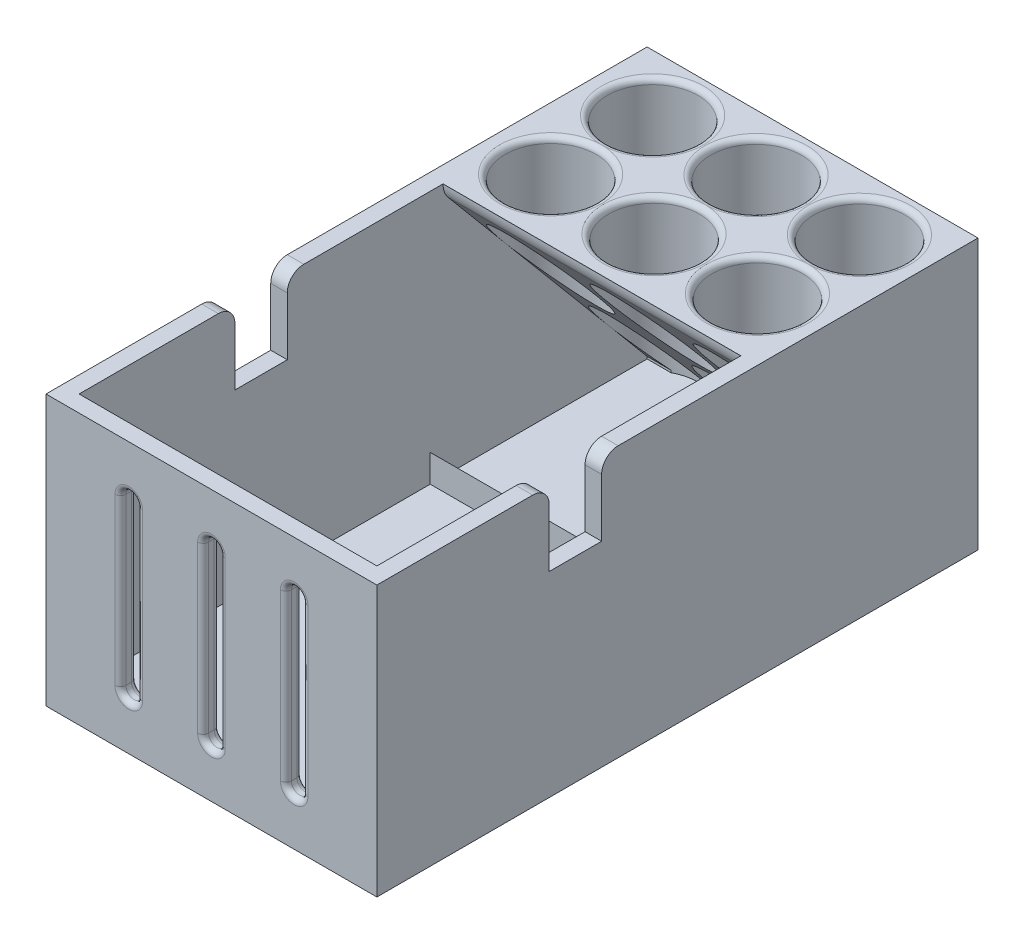
SolidWorks part; units mm, degrees
ref_plane "Front Plane" through (0, 0, 0) normal (0, 0, 1) x (1, 0, 0)
ref_plane "Top Plane" through (0, 0, 0) normal (0, 1, 0) x (1, 0, 0)
ref_plane "Right Plane" through (0, 0, 0) normal (1, 0, 0) x (0, 0, -1)
sketch "Base Plate" plane through (0, 0, 0) normal (0, 1, 0) x (1, 0, 0)
  line L1 (30, -53) -> (-30, -53)
  line L2 (30, -53) -> (30, 53)
  line L3 (30, 53) -> (-30, 53)
  line L4 (-30, -53) -> (-30, 53)
  line L5 (30, -53) -> (-30, 53) construction
  line L6 (30, 53) -> (-30, -53) construction
  point P0 (0, 0)
  dimension "D1" = 60
  dimension "D2" = 106
extrude "Base" add sketch "Base Plate" along normal blind 3
sketch "Sketch3" plane through (0, 3, 0) normal (0, 1, 0) x (1, 0, 0)
  line L0 (-30, -53) -> (30, -53) construction
  line L1 (-30, 53) -> (-27, 53)
  line L2 (-30, 53) -> (-30, -53)
  line L3 (-30, -53) -> (-27, -53)
  line L4 (-27, 53) -> (-27, -53)
  line L5 (0, 0) -> (0, 5) construction
  line L6 (27, 53) -> (27, -53)
  line L7 (30, -53) -> (27, -53)
  line L8 (30, 53) -> (30, -53)
  line L9 (30, 53) -> (27, 53)
  dimension "D1" = 3
extrude "Boss-Extrude2" add sketch "Sketch3" along normal blind 46
sketch "Sketch5" plane through (0, 3, 0) normal (0, 1, 0) x (1, 0, 0)
  line L0 (27, 53) -> (27, -53) construction
  line L1 (-27, 53) -> (27, 53)
  line L2 (-27, 53) -> (-27, 50)
  line L3 (-27, 50) -> (27, 50)
  line L4 (27, 53) -> (27, 50)
  dimension "D1" = 3
extrude "Boss-Extrude3" add sketch "Sketch5" along normal up to surface (46 mm away) up to face at (-28.5, 49, 0)
sketch "Sketch4" plane through (0, 49, 0) normal (0, 1, 0) x (1, 0, 0)
  line L0 (27, 50) -> (27, -53) construction
  line L1 (-27, 50) -> (27, 50)
  line L2 (-27, 50) -> (-27, 13)
  line L3 (-27, 13) -> (27, 13)
  line L4 (27, 50) -> (27, 13)
  dimension "D1" = 37
extrude "Boss-Extrude4" add sketch "Sketch4" against normal blind 1.5
sketch "Sketch7" plane through (27, 0, 0) normal (-1, 0, 0) x (0, 0, 1)
  line L0 (-50, 47.5) -> (-13, 47.5)
  line L1 (-13, 47.5) -> (-50, 3.4051)
  line L2 (-50, 47.5) -> (-50, 3) construction
  line L3 (-50, 3.4051) -> (-50, 47.5)
  dimension "D1" = 40
extrude "Boss-Extrude5" add sketch "Sketch7" along normal up to surface (54 mm away) up to face at (-27, 37, 5.25)
sketch "FluxPens" plane through (0, 49, 0) normal (0, 1, 0) x (1, 0, 0)
  line L0 (30, 53) -> (-30, 53) construction
  line L2 (-30, 53) -> (-30, -53) construction
  line L4 (-27, 13) -> (27, 13) construction
  line L5 (30, -53) -> (30, 53) construction
  line L6 (-18.75, 42.75) -> (18.75, 42.75) construction
  line L7 (-18.75, 24.25) -> (18.75, 24.25) construction
  line L8 (0, 24.25) -> (0, 42.75) construction
  circle A0 centre (-18.75, 42.75) radius 8.25
  circle A1 centre (-18.75, 24.25) radius 8.25
  circle A2 centre (0, 42.75) radius 8.25
  circle A3 centre (0, 24.25) radius 8.25
  circle A4 centre (18.75, 24.25) radius 8.25
  circle A5 centre (18.75, 42.75) radius 8.25
  dimension "D1" = 16.5
  dimension "D2" = 10.25
  dimension "D4" = 16.5
  dimension "D6" = 16.5
  dimension "D7" = 16.5
  dimension "D10" = 16.5
  dimension "D11" = 16.5
  dimension "D3" = 11.25
  dimension "D5" = 11.25
  dimension "D12" = 11.25
extrude "Cut-Extrude1" cut sketch "FluxPens" against normal up to surface (46 mm away) up to face at (-6.75, 3, 14.375)
fillet "Fillet1" radius 1 1 edges at (-18.75, 49, -34.5)
fillet "Fillet2" radius 1 1 edges at (0, 49, -34.5)
fillet "Fillet3" radius 1 1 edges at (-18.75, 49, -16)
fillet "Fillet4" radius 1 1 edges at (0, 49, -16)
fillet "Fillet5" radius 1 1 edges at (18.75, 49, -34.5)
fillet "Fillet6" radius 1 1 edges at (18.75, 49, -16)
sketch "Sketch12" plane through (-27, 0, 0) normal (1, 0, 0) x (0, 0, -1)
  line L0 (-20, 49) -> (-20, 35.5) construction
  line L1 (-53, 3) -> (50, 3) construction
  line L4 (-24.75, 35.5) -> (-24.75, 49)
  line L5 (-53, 49) -> (13, 49) construction
  line L6 (-24.75, 49) -> (-15.25, 49)
  line L7 (-15.25, 49) -> (-15.25, 35.5)
  line L8 (-24.75, 35.5) -> (-15.25, 35.5)
  dimension "D1" = 32.5
  dimension "D3" = 33
  dimension "D2" = 9.5
extrude "Roller Cut Out" cut sketch "Sketch12" against normal through all both and the other way through all
sketch "Sketch13" plane through (0, 0, 53) normal (0, 0, 1) x (1, 0, 0)
  line L1 (-30, 49) -> (30, 49)
  line L2 (-30, 49) -> (-30, 0)
  line L3 (-30, 0) -> (30, 0)
  line L4 (30, 49) -> (30, 0)
extrude "Boss-Extrude6" add sketch "Sketch13" along normal blind 3
sketch "Sketch14" plane through (0, 0, 56) normal (0, 0, 1) x (1, 0, 0)
  line L0 (0, 0) -> (0, 49) construction
  line L1 (-30, 0) -> (30, 0) construction
  line L2 (30, 49) -> (-30, 49) construction
  line L3 (-30, 24.5) -> (0, 24.5) construction
  line L4 (-30, 49) -> (-30, 0) construction
  line L5 (0, 24.5) -> (30, 24.5) construction
  line L6 (30, 0) -> (30, 49) construction
  line L7 (-15, 24.5) -> (-15, 0) construction
  line L8 (-15, 12.25) -> (0, 12.25) construction
  line L9 (-7.5, 12.25) -> (-7.5, 24.5) construction
  line L10 (-16.5, 9.5) -> (-16.5, 39.5)
  line L11 (-13.5, 39.5) -> (-13.5, 9.5)
  line L12 (15, 24.5) -> (15, 5.0514) construction
  line L13 (15, 5.0514) -> (0, 5.0514) construction
  line L14 (7.5, 5.0514) -> (7.5, 24.5) construction
  line L15 (13.5, 9.5) -> (13.5, 39.5)
  line L16 (-1.5, 39.5) -> (-1.5, 9.5)
  line L17 (1.5, 9.5) -> (1.5, 39.5)
  line L18 (16.5, 39.5) -> (16.5, 9.5)
  arc A0 (-13.5, 9.5) -> (-16.5, 9.5) centre (-15, 9.5) cw
  arc A1 (-16.5, 39.5) -> (-13.5, 39.5) centre (-15, 39.5) cw
  arc A2 (16.5, 9.5) -> (13.5, 9.5) centre (15, 9.5) cw
  arc A3 (13.5, 39.5) -> (16.5, 39.5) centre (15, 39.5) cw
  arc A8 (-1.5, 9.5) -> (1.5, 9.5) centre (0, 9.5) ccw
  arc A9 (1.5, 39.5) -> (-1.5, 39.5) centre (0, 39.5) ccw
  dimension "D4" = 1.5
  dimension "D5" = 15
  dimension "D6" = 15
extrude "Cut-Extrude6" cut sketch "Sketch14" against normal up to surface (3 mm away) up to face at (0, 37.5, 53)
fillet "Fillet7" radius 1 4 edges at (-15, 8, 53) (-16.5, 24.5, 53) (-15, 41, 53) (-13.5, 24.5, 53)
fillet "Fillet8" radius 1 4 edges at (0, 41, 53) (1.5, 24.5, 53) (0, 8, 53) (-1.5, 24.5, 53)
fillet "Fillet9" radius 1 4 edges at (15, 8, 53) (13.5, 24.5, 53) (15, 41, 53) (16.5, 24.5, 53)
fillet "Fillet10" radius 3 1 edges at (-28.5, 49, 15.25)
fillet "Fillet11" radius 3 1 edges at (-28.5, 49, 24.75)
fillet "Fillet12" radius 3 1 edges at (28.5, 49, 15.25)
fillet "Fillet13" radius 3 2 edges at (28.5, 49, 24.75)
fillet "Fillet14" radius 4 1 edges at (0, 47.5, -13)
fillet "Fillet15" radius 1 4 edges at (0, 41, 56) (-1.5, 24.5, 56) (0, 8, 56) (1.5, 24.5, 56)
fillet "Fillet16" radius 1 4 edges at (-15, 8, 56) (-13.5, 24.5, 56) (-15, 41, 56) (-16.5, 24.5, 56)
fillet "Fillet17" radius 1 4 edges at (15, 8, 56) (16.5, 24.5, 56) (15, 41, 56) (13.5, 24.5, 56)
sketch "Sketch16" plane through (-27, 0, 0) normal (1, 0, 0) x (0, 0, -1)
  line L0 (10.6685, 3) -> (10.6685, 8)
  line L1 (-53, 3) -> (50, 3) construction
  line L2 (10.6685, 8) -> (13, 3)
  line L3 (13, 3) -> (10.6685, 3)
  dimension "D1" = 65
  dimension "D2" = 5
extrude "Tool Catcher" add sketch "Sketch16" along normal up to surface (54 mm away) up to face at (27, 35.6029, 0.4444)
equation "\"WallSides\"= 3"
equation "\"D1@Sketch3\"=\"WallSides\""
equation "\"WallBack\"=3"
equation "\"D1@Sketch5\"=\"WallBack\""
equation "\"Tool_FluxPen\"= 16.5mm"
equation "\"D1@FluxPens\"=\"Tool_FluxPen\""
equation "\"Tool_FluxPen_DistanceBack\"= \"Tool_FluxPen\" / 2 + \"WallBack\""
equation "\"Tool_FluxPen_DistanceSide\"= \"Tool_FluxPen\" / 2 + \"WallSides\""
equation "\"D3@FluxPens\"=\"Tool_FluxPen_DistanceSide\""
equation "\"D4@FluxPens\"=\"Tool_FluxPen\""
equation "\"D6@FluxPens\"=\"Tool_FluxPen\""
equation "\"D7@FluxPens\"=\"Tool_FluxPen\""
equation "\"Tool_FluxPen_DistanceNext\"= \"Tool_FluxPen\" + 2"
equation "\"Tool_FluxPen_DistanceFront\"= \"Tool_FluxPen\" / 2 + 2"
equation "\"D10@FluxPens\"=\"Tool_FluxPen\""
equation "\"D11@FluxPens\"=\"Tool_FluxPen\""
equation "\"D12@FluxPens\"=\"Tool_FluxPen_DistanceSide\""
